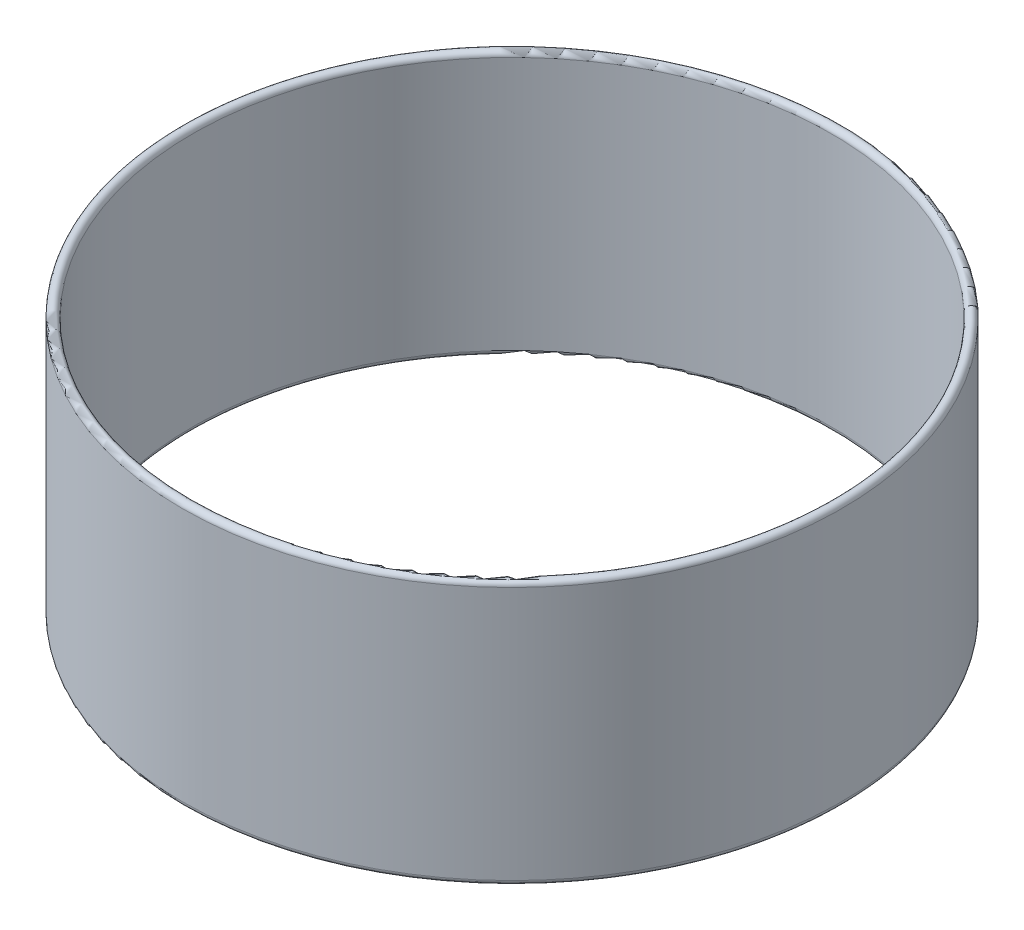
SolidWorks part; units mm, degrees
ref_plane "Front Plane" through (0, 0, 0) normal (0, 0, 1) x (1, 0, 0)
ref_plane "Top Plane" through (0, 0, 0) normal (0, 1, 0) x (1, 0, 0)
ref_plane "Right Plane" through (0, 0, 0) normal (1, 0, 0) x (0, 0, -1)
sketch "Shield Cross Section Sketch" plane through (0, 0, 0) normal (0, 1, 0) x (1, 0, 0)
  circle A0 centre (0, 0) radius 100
  circle A1 centre (0, 0) radius 97
  dimension "D1" = 200
  dimension "D2" = 3
extrude "Shield Extrude" add sketch "Shield Cross Section Sketch" along normal blind 80
fillet "Top Fillet" 2 edges at (0, 80, 97) (0, 80, 100) type full round first side face at (0, 80, 97) second side face at (0, 80, 100) middle face at (0, 80, 100)
fillet "Bottom Fillet" 2 edges at (0, 0, 97) (0, 0, 100) type full round first side face at (0, 78.5, 97) second side face at (0, 78.5, 100) middle face at (0, 0, 100)
